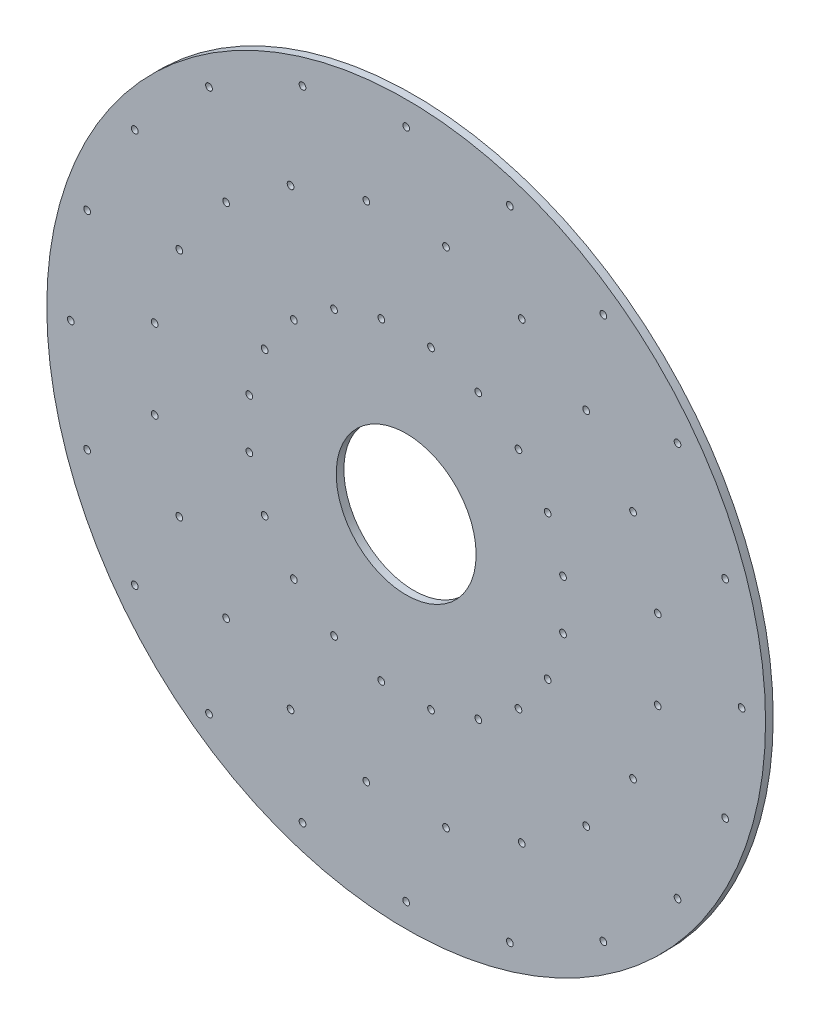
SolidWorks part; units mm, degrees
material "Corrugated Paper"
ref_plane "Front Plane" through (0, 0, 0) normal (0, 0, 1) x (1, 0, 0)
ref_plane "Top Plane" through (0, 0, 0) normal (0, 1, 0) x (1, 0, 0)
ref_plane "Right Plane" through (0, 0, 0) normal (1, 0, 0) x (0, 0, -1)
sketch "Sketch1" plane through (0, 0, 0) normal (0, 0, 1) x (1, 0, 0)
  circle A0 centre (0, 0) radius 187.5
  dimension "D1" = 375
extrude "Boss-Extrude1" add sketch "Sketch1" along normal blind 4
sketch "Sketch2" plane through (0, 0, 4) normal (0, 0, 1) x (1, 0, 0)
  circle A0 centre (0, 0) radius 36.5
  dimension "D1" = 73
extrude "Cut-Extrude1" cut sketch "Sketch2" against normal through all
sketch "Sketch3" plane through (0, 0, 4) normal (0, 0, 1) x (1, 0, 0)
  line L0 (0, -2.2) -> (0, 2.2) construction
  circle A0 centre (0, 175) radius 1.755
  circle A1 centre (0, 0) radius 187.5 construction
  dimension "D2" = 3.51
  dimension "D1" = 175
extrude "Cut-Extrude2" cut sketch "Sketch3" against normal through all
ref_axis "Axis1" through (0, 0, -0.2) along (0, 0, 1)
pattern_circular "CirPattern1" count 20 over 360 about axis through (0, 0, -0.2) along (0, 0, 1) of "Cut-Extrude2"
sketch "Sketch4" plane through (0, 0, 4) normal (0, 0, 1) x (1, 0, 0)
  line L0 (0, 175) -> (54.078, 166.4349) construction
  line L1 (27.039, 170.7174) -> (0, 0) construction
  circle A0 centre (20.7816, 131.2099) radius 1.755
  circle A1 centre (12.9599, 81.8255) radius 1.755
  point P7 (20.7816, 131.2099)
  point P8 (12.9599, 81.8255)
  dimension "D3" = 3.51
  dimension "D4" = 3.51
  dimension "D1" = 50
  dimension "D2" = 40
extrude "Cut-Extrude3" cut sketch "Sketch4" against normal through all
pattern_circular "CirPattern2" count 20 over 360 about axis through (0, 0, -0.2) along (0, 0, 1) of "Cut-Extrude3"
equation "\"D4@Sketch4\"=\"D3@Sketch4\""
